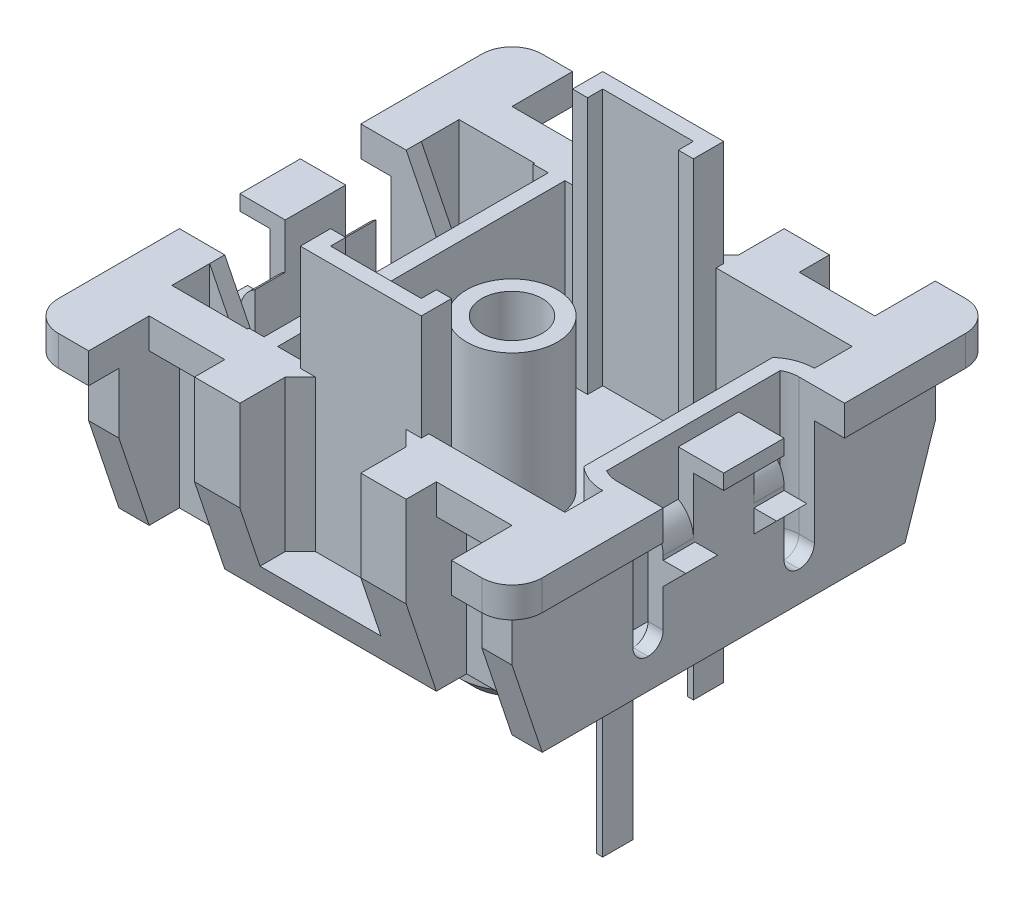
SolidWorks part; units mm, degrees
ref_plane "Plan de face" through (0, 0, 0) normal (0, 0, 1) x (1, 0, 0)
ref_plane "Plan de dessus" through (0, 0, 0) normal (0, 1, 0) x (1, 0, 0)
ref_plane "Plan de droite" through (0, 0, 0) normal (1, 0, 0) x (0, 0, -1)
sketch "Esquisse1" plane through (0, 0, 0) normal (0, 1, 0) x (1, 0, 0)
  line L0 (6, 8) -> (6, 6)
  line L5 (-7, -8) -> (7, -8)
  line L7 (-7, 8) -> (7, 8)
  line L8 (8, -7) -> (8, 7)
  line L9 (-8, -8) -> (8, 8) construction
  line L10 (-8, 8) -> (8, -8) construction
  line L11 (6, 6) -> (3.5, 6)
  line L12 (3.5, 6) -> (3.5, 7)
  line L13 (3.5, 7) -> (2, 7)
  line L14 (2, 7) -> (2, 6.5)
  line L15 (2, 6.5) -> (-2, 6.5)
  line L16 (-2, 6.5) -> (-2, 7)
  line L17 (-2, 7) -> (-3.5, 7)
  line L18 (-3.5, 7) -> (-3.5, 6)
  line L19 (-3.5, 6) -> (-6, 6)
  line L20 (-6, 6) -> (-6, 8)
  line L21 (6, 8) -> (-6, 8)
  line L22 (8, 0) -> (-8, 0)
  line L23 (-8, 0) -> (8, 0)
  line L24 (6, -8) -> (6, -6)
  line L25 (6, -6) -> (3.5, -6)
  line L26 (3.5, -6) -> (3.5, -7)
  line L27 (3.5, -7) -> (2, -7)
  line L28 (2, -7) -> (2, -6.5)
  line L29 (2, -6.5) -> (-2, -6.5)
  line L30 (-2, -6.5) -> (-2, -7)
  line L31 (-2, -7) -> (-3.5, -7)
  line L32 (-3.5, -7) -> (-3.5, -6)
  line L33 (-3.5, -6) -> (-6, -6)
  line L34 (-6, -6) -> (-6, -8)
  line L35 (6, -8) -> (-6, -8)
  line L36 (-8, 3) -> (-7, 3)
  line L37 (-7, 3) -> (-7, 1)
  line L38 (-7, 1) -> (-8, 1)
  line L39 (-8, 1) -> (-8, -1)
  line L40 (-8, -1) -> (-7, -1)
  line L41 (-7, -1) -> (-7, -3)
  line L42 (-7, -3) -> (-8, -3)
  line L43 (-8, -3) -> (-8, 3)
  line L44 (-8, 7) -> (-8, 3)
  line L45 (-8, -7) -> (-8, -3)
  line L46 (0, 6.5) -> (0, -6.5)
  line L47 (0, -6.5) -> (0, 6.5)
  line L48 (-8, -3) -> (-8, -1)
  line L49 (-8, 3) -> (-8, 1)
  line L50 (-8, -7) -> (-8, 7)
  line L51 (8, 3) -> (8, 1)
  line L52 (8, -3) -> (8, -1)
  line L53 (8, -3) -> (8, 3)
  line L54 (7, -3) -> (8, -3)
  line L55 (7, -1) -> (7, -3)
  line L56 (8, -1) -> (7, -1)
  line L57 (8, 1) -> (8, -1)
  line L58 (7, 1) -> (8, 1)
  line L59 (7, 3) -> (7, 1)
  line L60 (8, 3) -> (7, 3)
  line L61 (8, -7) -> (8, 7)
  arc A0 (-8, 7) -> (-7, 8) centre (-7, 7) cw
  arc A1 (8, -7) -> (7, -8) centre (7, -7) cw
  arc A2 (8, 7) -> (7, 8) centre (7, 7) ccw
  arc A3 (-8, -7) -> (-7, -8) centre (-7, -7) ccw
  point P0 (0, 0)
  dimension "D3" = 1
  dimension "D1" = 16
  dimension "D2" = 16
  dimension "D4" = 2
  dimension "D5" = 2
  dimension "D6" = 2.5
  dimension "D7" = 2.5
  dimension "D8" = 4
  dimension "D9" = 1.5
  dimension "D10" = 1.5
  dimension "D11" = 1
  dimension "D12" = 1
  dimension "D13" = 0.5
  dimension "D14" = 0.5
  dimension "D15" = 14
  dimension "D16" = 2
  dimension "D17" = 2
  dimension "D18" = 2
  dimension "D19" = 1
  dimension "D20" = 1
  dimension "D21" = 1
  dimension "D22" = 1
  dimension "D23" = 1
  dimension "D24" = 1
extrude "Boss.-Extru.1" add sketch "Esquisse1" along normal blind 1 contours A0 L44 L36 L37 L38 L39 L23 L46 L15 L16 L17 L18 L19 L20 L7 | L8 A2 L7 L0 L11 L12 L13 L14 L15 L46 L22 L58 L59 L60 | L45 A3 L5 L34 L33 L32 L31 L30 L29 L46 L23 L39 L40 L41 L42 | A1 L8 L54 L55 L56 L22 L46 L29 L28 L27 L26 L25 L24 L5 region at (3.9869, 0, -3.4872) region at (-3.9869, 0, -3.4872) region at (3.9869, 0, 3.4872) region at (-3.9869, 0, 3.4872)
sketch "Esquisse2" plane through (0, 0, 0) normal (0, -1, 0) x (1, 0, 0)
  line L0 (6, 7) -> (6, 5)
  line L1 (-7, 7) -> (7, 7)
  line L2 (-7, 7) -> (-7, -7)
  line L3 (-7, -7) -> (7, -7)
  line L4 (7, 7) -> (7, -7)
  line L5 (-7, 7) -> (7, -7) construction
  line L6 (-7, -7) -> (7, 7) construction
  line L7 (6, 8) -> (6, 6) construction
  line L8 (6, 5) -> (3.5, 5)
  line L9 (3.5, 5) -> (3.5, 7)
  line L10 (3.5, 7) -> (-3.5, 7)
  line L11 (-3.5, 7) -> (-3.5, 5)
  line L12 (-3.5, 5) -> (-6, 5)
  line L13 (-6, 5) -> (-6, 7)
  line L14 (-6, 6) -> (-6, 8) construction
  line L15 (-6, 7) -> (6, 7)
  line L16 (7, 0) -> (-7, 0)
  line L17 (-7, 0) -> (7, 0)
  line L18 (-6, -7) -> (6, -7)
  line L19 (-6, -5) -> (-6, -7)
  line L20 (-3.5, -5) -> (-6, -5)
  line L21 (-3.5, -7) -> (-3.5, -5)
  line L22 (3.5, -7) -> (-3.5, -7)
  line L23 (3.5, -5) -> (3.5, -7)
  line L24 (6, -5) -> (3.5, -5)
  line L25 (6, -7) -> (6, -5)
  point P0 (0, 0)
  line M6 (2, 6.5) -> (-2, 6.5)
  line M7 (-2, 6.5) -> (-2, 7)
  line M8 (-2, 7) -> (-3.5, 7)
  line M9 (-3.5, 7) -> (-3.5, 6)
  line M11 (-6, 6) -> (-6, 8)
  line M16 (-7, 3) -> (-7, 1)
  line M20 (-7, -1) -> (-7, -3)
  line M25 (-6, -8) -> (-6, -6)
  line M27 (-3.5, -6) -> (-3.5, -7)
  line M28 (-3.5, -7) -> (-2, -7)
  line M29 (-2, -7) -> (-2, -6.5)
  line M30 (-2, -6.5) -> (2, -6.5)
  line M31 (2, -6.5) -> (2, -7)
  line M32 (2, -7) -> (3.5, -7)
  line M33 (3.5, -7) -> (3.5, -6)
  line M35 (6, -6) -> (6, -8)
  line M40 (7, -3) -> (7, -1)
  line M44 (7, 1) -> (7, 3)
  line M49 (6, 8) -> (6, 6)
  line M51 (3.5, 6) -> (3.5, 7)
  line M52 (3.5, 7) -> (2, 7)
  line M53 (2, 7) -> (2, 6.5)
  dimension "D1" = 14
  dimension "D2" = 14
  dimension "D3" = 2.5
  dimension "D4" = 2.5
  dimension "D5" = 7
  dimension "D6" = 1
  dimension "D7" = 1
  dimension "D8" = 2
  dimension "D9" = 2
  dimension "D10" = 2
  dimension "D11" = 2
extrude "Boss.-Extru.3" add sketch "Esquisse2" along normal blind 5 contours L16 L4 L1 L0 L8 L9 L11 L12 L13 L2 M44 M49 M51 M52 M53 M6 M7 M8 M9 M11 M16 | L25 L3 L4 L16 L2 L19 L20 L21 L23 L24 M35 M40 M20 M25 M27 M28 M29 M30 M31 M32 M33 region at (0, 0, 3.1337) region at (0, 0, -3.1337)
sketch "Esquisse3" plane through (7, 0, 0) normal (1, 0, 0) x (0, 0, -1)
  line L0 (-7, -2) -> (-6, -5)
  line L1 (-7, -5) -> (-7, 0) construction
  line L2 (-7, -5) -> (7, -5) construction
  line L3 (-6, -5) -> (-7, -5)
  line L4 (-7, -5) -> (-7, -2)
  line L5 (0, 1) -> (0, -5)
  line L6 (-1, 1) -> (1, 1) construction
  line L7 (0, -5) -> (0, 1)
  line L8 (7, -5) -> (7, -2)
  line L9 (6, -5) -> (7, -5)
  line L10 (7, -2) -> (6, -5)
  line M7 (-7, 0) -> (-7, -5)
  line M8 (-7, -5) -> (7, -5)
  line M9 (7, -5) -> (7, 0)
  dimension "D1" = 3
  dimension "D2" = 1
extrude "Enlèv. mat.-Extru.1" cut sketch "Esquisse3" against normal through all contours L0 M7 M8 | L10 M9 M8 region at (7, -4, -6.6667) region at (7, -4, 6.6667)
sketch "Esquisse5" plane through (0, 1, 0) normal (0, 1, 0) x (1, 0, 0)
  line L0 (6.5, 0) -> (-6.5, 0)
  line L1 (6.5, 4.75) -> (-6.5, 4.75)
  line L2 (6.5, 4.75) -> (6.5, -4.75)
  line L3 (6.5, -4.75) -> (-6.5, -4.75)
  line L4 (-6.5, 4.75) -> (-6.5, -4.75)
  line L5 (6.5, 4.75) -> (-6.5, -4.75) construction
  line L6 (6.5, -4.75) -> (-6.5, 4.75) construction
  line L7 (2, 6.5) -> (-2, 6.5)
  line L8 (2, 6.5) -> (2, 4)
  line L10 (-2, 6.5) -> (-2, 4)
  line L12 (1.5, 4) -> (1.5, 4.5)
  line L13 (1.5, 4.5) -> (-1.5, 4.5)
  line L14 (-1.5, 4) -> (-1.5, 4.5)
  line L15 (-4, 4.75) -> (-4, 3.5)
  line L16 (-1.5, -4) -> (-1.5, -4.5)
  line L17 (1.5, -4.5) -> (-1.5, -4.5)
  line L18 (1.5, -4) -> (1.5, -4.5)
  line L20 (-2, -6.5) -> (-2, -4)
  line L22 (2, -6.5) -> (2, -4)
  line L23 (2, -6.5) -> (-2, -6.5)
  line L26 (-3, 4.75) -> (-3, -4.75)
  line L29 (-7, 3) -> (-6.5, 3)
  line L30 (-7, 3) -> (-7, 2)
  line L31 (-7, 2) -> (-6.5, 2)
  line L33 (-7, -3) -> (-6.5, -3)
  line L34 (-7, -3) -> (-7, -2)
  line L35 (-7, -2) -> (-6.5, -2)
  line L37 (7, 3) -> (6.5, 3)
  line L38 (7, 3) -> (7, 2)
  line L39 (7, 2) -> (6.5, 2)
  line L41 (7, -3) -> (6.5, -3)
  line L42 (7, -3) -> (7, -2)
  line L43 (7, -2) -> (6.5, -2)
  line L45 (6.5, 3) -> (6.49, 3)
  line L47 (6.5, -3) -> (6.49, -3)
  line L48 (5.5, 2.01) -> (5.5, -2.01)
  line L49 (-2, 5.25) -> (-1.5, 4.75)
  line L53 (1.5, 4.75) -> (2, 5.5)
  line L54 (-2, -5.25) -> (-1.5, -4.75)
  line L59 (1.5, -4.75) -> (2, -5.5)
  line L60 (-6.5, -3) -> (-4, -3)
  line L61 (-6.5, 3) -> (-4, 3)
  line L63 (-6.5, 3.5) -> (-4, 3.5)
  line L69 (-6.5, -3) -> (-6.5, -3.5)
  line L70 (-6.5, -3.5) -> (-4, -3.5)
  line L72 (-4, 3) -> (-4, -3)
  line L73 (-4, -3.5) -> (-4, -4.75)
  line L74 (-4, -4.75) -> (-4, -3.5)
  line L75 (-2, 4) -> (-1.5, 4)
  line L76 (1.5, 4) -> (2, 4)
  line L77 (-1.5, -4) -> (-2, -4)
  line L78 (1.5, -4) -> (2, -4)
  line L79 (-1.5, -4.75) -> (1.5, -4.75)
  line L80 (-6.5, -3.5) -> (-6.5, -3)
  line L81 (-6.5, 3.5) -> (-6.5, 3)
  line L82 (-4, 4.75) -> (-3, 4.75)
  line L83 (-4, -4.75) -> (-3, -4.75)
  line L84 (7.5, 1.5) -> (6.5, 1.5)
  line L85 (7.5, 3.5) -> (7.5, 1.5)
  line L86 (7.5, 3.5) -> (6.5, 3.5)
  line L87 (6.5, 3.5) -> (6.49, 3.5)
  line L89 (6.5, -3.5) -> (6.49, -3.5)
  line L90 (7.5, -3.5) -> (6.5, -3.5)
  line L91 (7.5, -3.5) -> (7.5, -1.5)
  line L92 (7.5, -1.5) -> (6.5, -1.5)
  line L93 (5.5, 2.01) -> (5.5, 3.1236)
  line L94 (5.5, 3.1236) -> (5.5, -2.01)
  line L95 (5.5, -2.01) -> (5.5, -3.1236)
  line L96 (5.5, -3.1236) -> (5.5, 2.01)
  line L98 (5, 2.01) -> (5, -2.01) construction
  arc A0 (6.49, -3) -> (5.5, -2.01) centre (6.49, -2.01) cw
  arc A1 (6.49, 3) -> (5.5, 2.01) centre (6.49, 2.01) ccw
  arc A2 (6.49, 3.5) -> (5, 2.01) centre (6.49, 2.01) ccw
  arc A3 (6.49, -3.5) -> (5, -2.01) centre (6.49, -2.01) cw
  point P1 (0, 0)
  point P40 (-2, 4.75)
  point P54 (5.5, -3)
  point P57 (5.5, 3)
  dimension "D21" = 0.99
  dimension "D1" = 13
  dimension "D2" = 9.5
  dimension "D3" = 4
  dimension "D4" = 2.5
  dimension "D5" = 0.5
  dimension "D6" = 3
  dimension "D7" = 0.5
  dimension "D8" = 0.5
  dimension "D9" = 1
  dimension "D10" = 1
  dimension "D11" = 0.5
  dimension "D12" = 0.5
  dimension "D13" = 0.5
  dimension "D14" = 1
  dimension "D15" = 1
  dimension "D16" = 1
  dimension "D17" = 0.5
  dimension "D18" = 0.5
  dimension "D19" = 6
  dimension "D20" = 1
  dimension "D22" = 0.5
  dimension "D23" = 0.5
  dimension "D24" = 0.5
  dimension "D27" = 2.5
  dimension "D28" = 0.5
extrude "Enlèv. mat.-Extru.12" cut sketch "Esquisse5" against normal blind 5 contours A1 L45 L2 L1 L8 L76 L12 L13 L14 L75 L10 L26 L0 L48 | L47 A0 L48 L0 L26 L3 L20 L77 L16 L17 L18 L78 L22 L2 | L72 L61 L4 L0 | L72 L0 L4 L60 | L73 L70 L4 L3 | L4 L63 L15 L1 region at (1.4572, 1, 2.3531) region at (1.4572, 1, -2.3531) region at (-5.25, 1, 1.5) region at (-5.25, 1, -1.5) region at (-5.25, 1, -4.125) region at (-5.25, 1, 4.125)
sketch "Esquisse8" plane through (0, 1, -1) normal (0, -1, 0) x (1, 0, 0)
  point P1 (0, 1)
  point P54 (5.5002, -2.0207)
  point P57 (5.488, 3.9793)
  line B0 (6.5, 1) -> (-6.5, 1)
  line B1 (6.5, 6) -> (-6.5, 6)
  line B2 (6.5, 6) -> (6.5, -4)
  line B3 (6.5, -4) -> (-6.5, -4)
  line B4 (-6.5, 6) -> (-6.5, -4)
  line B5 (6.5, 6) -> (-6.5, -4) construction
  line B6 (6.5, -4) -> (-6.5, 6) construction
  line B7 (2, 7.5) -> (-2, 7.5)
  line B8 (2, 7.5) -> (2, 5)
  line B9 (-2, 7.5) -> (-2, 5)
  line B10 (1.5, 5) -> (1.5, 5.5)
  line B11 (1.5, 5.5) -> (-1.5, 5.5)
  line B12 (-1.5, 5) -> (-1.5, 5.5)
  line B13 (-4, 6) -> (-4, 4.5)
  line B14 (-1.5, -3) -> (-1.5, -3.5)
  line B15 (1.5, -3.5) -> (-1.5, -3.5)
  line B16 (1.5, -3) -> (1.5, -3.5)
  line B17 (-2, -5.5) -> (-2, -3)
  line B18 (2, -5.5) -> (2, -3)
  line B19 (2, -5.5) -> (-2, -5.5)
  line B20 (-3, 6) -> (-3, -4)
  line B21 (-7, 4) -> (-6.5, 4)
  line B22 (-7, 4) -> (-7, 3)
  line B23 (-7, 3) -> (-6.5, 3)
  line B24 (-7, -2) -> (-6.5, -2)
  line B25 (-7, -2) -> (-7, -1)
  line B26 (-7, -1) -> (-6.5, -1)
  line B27 (7, 4) -> (6.5, 4)
  line B28 (7, 4) -> (7, 3)
  line B29 (7, 3) -> (6.5, 3)
  line B30 (7, -2) -> (6.5, -2)
  line B31 (7, -2) -> (7, -1)
  line B32 (7, -1) -> (6.5, -1)
  line B33 (6.5, 4) -> (6.49, 4)
  line B34 (6.5, -2) -> (6.49, -2)
  line B35 (5.5, 3.01) -> (5.5, -1.01)
  line B36 (-2, 6.5) -> (-1.5, 6)
  line B37 (1.5, 6) -> (2, 6.5)
  line B38 (-2, -4.5) -> (-1.5, -4)
  line B39 (1.5, -4) -> (2, -4.5)
  line B40 (-6.5, -2) -> (-4, -2)
  line B41 (-6.5, 4) -> (-4, 4)
  line B42 (-6.5, 4.5) -> (-4, 4.5)
  line B43 (-6.5, -2) -> (-6.5, -2.5)
  line B44 (-6.5, -2.5) -> (-4, -2.5)
  line B45 (-4, 4) -> (-4, -2)
  line B46 (-4, -2.5) -> (-4, -4)
  line B47 (-4, -4) -> (-4, -2.5)
  line B48 (-2, 5) -> (-1.5, 5)
  line B49 (1.5, 5) -> (2, 5)
  line B50 (-1.5, -3) -> (-2, -3)
  line B51 (1.5, -3) -> (2, -3)
  line B52 (-1.5, -4) -> (1.5, -4)
  line B53 (-6.5, -2.5) -> (-6.5, -2)
  line B54 (-6.5, 4.5) -> (-6.5, 4)
  line B55 (-4, 6) -> (-3, 6)
  line B56 (-4, -4) -> (-3, -4)
  arc B57 (6.49, -2) -> (5.5, -1.01) centre (6.49, -1.01) cw
  arc B58 (6.49, 4) -> (5.5, 3.01) centre (6.49, 3.01) ccw
  dimension "D19" = 6
  dimension "D20" = 1
sketch_block_instance "Bloc1-1"
sketch_block "Bloc1" parameters "D18"=0.99, "D1"=13, "D2"=10, "D3"=4, "D4"=2.5, "D5"=0.5, "D6"=3, "D7"=0.5, "D8"=0.5, "D9"=1, "D10"=1, "D11"=0.5, "D12"=0.5, "D13"=1, "D14"=1, "D15"=1, "D16"=0.5, "D17"=0.5, "D19"=0.5, "D20"=0.5, "D21"=2.5, "D22"=0.5, "D23"=0.5
extrude "Enlèv. mat.-Extru.17" cut sketch "Esquisse8" along normal blind 5 contours B3 B39 B18 B19 B17 B38 | B37 B1 B36 B9 B7 B8 region at (0, 1, 5.7754) region at (0, 1, -5.7754)
sketch "Esquisse10" plane through (0, 1, 0) normal (0, 1, 0) x (1, 0, 0)
  line L5 (0, 4.5) -> (0, -4.5)
  line L10 (1.5, 4.5) -> (-1.5, 4.5) construction
  line L11 (1.5, -4.5) -> (-1.5, -4.5) construction
  line L12 (0, -4.5) -> (0, 4.5)
  line L22 (-8, 3) -> (-5, 3)
  line L23 (-8, 3) -> (-8, 2)
  line L24 (-8, 2) -> (-5, 2)
  line L25 (-5, 3) -> (-5, 2)
  line L26 (-8, -3) -> (-5, -3)
  line L27 (-8, -3) -> (-8, -2)
  line L28 (-8, -2) -> (-5, -2)
  line L29 (-5, -3) -> (-5, -2)
  dimension "D1" = 3
  dimension "D2" = 1
  dimension "D3" = 3
  dimension "D4" = 1
extrude "Enlèv. mat.-Extru.20" cut sketch "Esquisse10" against normal blind 5 contours L25 L22 L23 L24 | L26 L29 L28 L27 region at (-6.5, 1, -2.5) region at (-6.5, 1, 2.5)
sketch "Esquisse11" plane through (0, 1, 0) normal (0, 1, 0) x (1, 0, 0)
sketch "Esquisse12" plane through (0, 1, 0) normal (0, 1, 0) x (1, 0, 0)
  line L1 (6.49, -3) -> (7, -3)
  line L2 (6, 2.8702) -> (6, -2.8702)
  line L3 (6, 2.8702) -> (6, -2.8702)
  line L4 (7, -3) -> (7, -2)
  line L5 (7, -1) -> (7, -3) construction
  line L6 (7, -2) -> (6.5, -2)
  line L7 (6.5, -2) -> (6.5, 2)
  line L8 (6.5, 2) -> (7, 2)
  line L9 (7, 3) -> (7, 1) construction
  line L10 (7, 2) -> (7, 3)
  line L11 (7, 3) -> (6.49, 3)
  arc A8 (6, -2.8702) -> (6.49, -3) centre (6.49, -2.01) ccw
  arc A9 (6.49, 3) -> (6, 2.8702) centre (6.49, 2.01) ccw
  arc A10 (6, -2.8702) -> (6.49, -3) centre (6.49, -2.01) ccw
  arc A11 (6.49, 3) -> (6, 2.8702) centre (6.49, 2.01) ccw
  dimension "D2" = 4
  dimension "D3" = 1
  dimension "D4" = 1
  dimension "D5" = 0.5
  dimension "D6" = 0.5
  dimension "D1" = 0.5
extrude "Enlèv. mat.-Extru.21" cut sketch "Esquisse12" against normal blind 5
sketch "Esquisse13" plane through (0, -5, 0) normal (0, -1, 0) x (1, 0, 0)
  circle A0 centre (0, 0) radius 1.75
  dimension "D1" = 3.5
extrude "Boss.-Extru.4" add sketch "Esquisse13" along normal blind 4
chamfer "Chanfrein1" distance 0.5 1 edges at (0, -9, -1.75)
sketch "Esquisse14" plane through (0, -9, 0) normal (0, -1, 0) x (1, 0, 0)
  circle A0 centre (0, 0) radius 0.75
  dimension "D1" = 1.5
extrude "Enlèv. mat.-Extru.22" cut sketch "Esquisse14" against normal blind 0.1
sketch "Esquisse15" plane through (0, -4, 0) normal (0, 1, 0) x (1, 0, 0)
  circle A0 centre (0, 0) radius 1
  circle A1 centre (0, 0) radius 1.5
  dimension "D1" = 2
  dimension "D2" = 3
extrude "Boss.-Extru.5" add sketch "Esquisse15" along normal blind 5
sketch "Esquisse16" plane through (0, -4, 0) normal (0, 1, 0) x (1, 0, 0)
  circle A0 centre (0, 0) radius 1
extrude "Enlèv. mat.-Extru.23" cut sketch "Esquisse16" against normal blind 4
sketch "Esquisse17" plane through (0, -5, 0) normal (0, -1, 0) x (1, 0, 0)
  line L1 (3, -4) -> (2.8, -4)
  line L2 (3, -4) -> (3, -3)
  line L3 (3, -3) -> (2.8, -3)
  line L4 (2.8, -4) -> (2.8, -3)
  line L5 (6, 3) -> (5.8, 3)
  line L6 (6, 3) -> (6, 2)
  line L7 (6, 2) -> (5.8, 2)
  line L8 (5.8, 3) -> (5.8, 2)
  dimension "D1" = 1
  dimension "D2" = 0.2
  dimension "D3" = 1
  dimension "D4" = 0.2
extrude "Boss.-Extru.6" add sketch "Esquisse17" along normal blind 5 contours L6 L7 L8 L5 | L2 L3 L4 L1
sketch "Esquisse18" plane through (0, 0, 3.5) normal (0, 0, 1) x (1, 0, 0)
  line L0 (-6.5, 1) -> (-6.5, -1)
  line L1 (-6.5, -4) -> (-6.5, 1) construction
  line L2 (-6.5, -1) -> (-5.5, -1)
  line L3 (-5.5, -1) -> (-4.5, -1)
  line L4 (-4.5, -1) -> (-3.5, -1)
  line L5 (-3.5, -1) -> (-3.5, 1)
  line L6 (-3.5, 1) -> (-4.5, -1)
  line L7 (-5.5, -1) -> (-6.5, 1)
  line L8 (-3.5, 1) -> (-6.5, 1)
  line M6 (-4, 1) -> (-6.5, 1)
  line M9 (-4, -4) -> (-4, 1)
  dimension "D1" = 3
  dimension "D2" = 1
  dimension "D3" = 1
  dimension "D4" = 1
  dimension "D5" = 2
extrude "Enlèv. mat.-Extru.24" cut sketch "Esquisse18" against normal blind 8.2 and the other way blind 1.2 contours L7 L3 L6 M9 M6 | L6 L8 M9 region at (-5.0778, 0.1333, 3.5) region at (-3.8333, 0.6667, 3.5)
sketch "Esquisse19" plane through (0, 1, 0) normal (0, 1, 0) x (1, 0, 0)
  line L1 (2, 4) -> (-2, 4)
  line L2 (2, 4) -> (2, 5)
  line L3 (2, 5) -> (-2, 5)
  line L4 (-2, 4) -> (-2, 5)
  line L5 (2, -4) -> (-2, -4)
  line L6 (2, -4) -> (2, -5)
  line L7 (2, -5) -> (-2, -5)
  line L8 (-2, -4) -> (-2, -5)
  line L9 (-1.5, 4.5) -> (1.5, 4.5)
  line L10 (-1.5, 4.5) -> (-1.5, 4)
  line L11 (-1.5, 4) -> (1.5, 4)
  line L12 (1.5, 4.5) -> (1.5, 4)
  line L13 (1.5, -4) -> (-1.5, -4)
  line L14 (1.5, -4) -> (1.5, -4.5)
  line L15 (1.5, -4.5) -> (-1.5, -4.5)
  line L16 (-1.5, -4) -> (-1.5, -4.5)
  dimension "D1" = 4
  dimension "D2" = 1
  dimension "D3" = 1
  dimension "D4" = 4
extrude "Boss.-Extru.7" add sketch "Esquisse19" along normal blind 3.5 contours L9 L12 L1 L2 L3 L4 L10 | L16 L5 L8 L7 L6 L14 L15 region at (0, 1, -4.65) region at (0, 1, 4.65)
sketch "Esquisse20" plane through (0, 1, 0) normal (0, 1, 0) x (1, 0, 0)
  line L0 (-6.5, 2) -> (-6.5, -2) construction
  line L1 (-7, 2) -> (-6.5, 2)
  line L2 (-7, 2) -> (-7, 1)
  line L3 (-7, 1) -> (-6.5, 1)
  line L4 (-6.5, 2) -> (-6.5, 1)
  line L5 (6.5, -2) -> (6.5, 2) construction
  line L6 (-7, -1) -> (-6.5, -1)
  line L7 (-7, -1) -> (-7, -2)
  line L8 (-7, -2) -> (-6.5, -2)
  line L9 (-6.5, -1) -> (-6.5, -2)
  line L10 (7, 1) -> (6.5, 1)
  line L11 (7, 1) -> (7, 2)
  line L12 (7, 2) -> (6.5, 2)
  line L13 (6.5, 1) -> (6.5, 2)
  line L14 (7, -2) -> (6.5, -2)
  line L15 (7, -2) -> (7, -1)
  line L16 (7, -1) -> (6.5, -1)
  line L17 (6.5, -2) -> (6.5, -1)
extrude "Enlèv. mat.-Extru.25" cut sketch "Esquisse20" against normal blind 1.5
sketch "Esquisse22" plane through (-7, 0, 0) normal (-1, 0, 0) x (0, 0, 1)
  line L0 (-2, -0.5) -> (-2, -4) construction
  line L1 (-2, -1.5) -> (-1, -1.5)
  line L2 (-2, -1.5) -> (-2, -2.25)
  line L3 (-2, -2.25) -> (-1, -2.25)
  line L4 (-1, -1.5) -> (-1, -2.25)
  line L5 (2, -0.5) -> (2, -4) construction
  line L6 (2, -1.5) -> (1, -1.5)
  line L7 (2, -1.5) -> (2, -2.25)
  line L8 (2, -2.25) -> (1, -2.25)
  line L9 (1, -1.5) -> (1, -2.25)
  dimension "D1" = 0.75
  dimension "D2" = 0.75
  dimension "D3" = 1
  dimension "D4" = 1
extrude "Boss.-Extru.8" add sketch "Esquisse22" along normal blind 0.75
chamfer "Chanfrein2" distance 0.75 angle 45 2 edges at (-7.75, -2.25, 1.5) (-7.75, -2.25, -1.5)
fillet "Congé1" radius 1 2 edges at (-7, -0.5, -1.5) (-7, -0.5, 1.5) first distance on face at (-7, -1.8077, 0)
sketch "Esquisse23" plane through (0, 0, 0) normal (0, -1, 0) x (1, 0, 0)
  line L0 (-7, 6) -> (-7, -6) construction
  line L1 (-8, 1) -> (-7, 1)
  line L2 (-8, 1) -> (-8, -1)
  line L3 (-8, -1) -> (-7, -1)
  line L4 (-7, 1) -> (-7, -1)
  line L5 (-7, 1) -> (-7, -1) construction
extrude "Enlèv. mat.-Extru.26" cut sketch "Esquisse23" against normal blind 0.5
sketch "Esquisse24" plane through (7, 0, 0) normal (1, 0, 0) x (0, 0, -1)
  line L0 (-2, -4) -> (-2, -0.5) construction
  line L1 (2, -4) -> (2, -0.5) construction
  line L2 (-2, -1.5) -> (-0.9498, -1.5)
  line L3 (-2, -1.5) -> (-2, -2.25)
  line L4 (-2, -2.25) -> (-0.9498, -2.25)
  line L5 (-0.9498, -1.5) -> (-0.9498, -2.25)
  line L6 (2, -1.5) -> (1, -1.5)
  line L7 (2, -1.5) -> (2, -2.25)
  line L8 (2, -2.25) -> (1, -2.25)
  line L9 (1, -1.5) -> (1, -2.25)
  dimension "D1" = 0.75
  dimension "D2" = 0.75
  dimension "D3" = 1
  dimension "D4" = 1.0502
extrude "Boss.-Extru.9" add sketch "Esquisse24" along normal blind 0.75
chamfer "Chanfrein3" distance 0.75 angle 45 2 edges at (7.75, -2.25, 1.4749) (7.75, -2.25, -1.5)
fillet "Congé2" radius 1 2 edges at (7, -0.5, -1.5) (7, -0.5, 1.5) first distance on face at (7, -1.8077, -0.0039)
sketch "Esquisse25" plane through (0, 0, 0) normal (0, -1, 0) x (1, 0, 0)
  line L1 (8, 1) -> (7, 1)
  line L2 (8, 1) -> (8, -1)
  line L3 (8, -1) -> (7, -1)
  line L4 (7, 1) -> (7, -1)
extrude "Enlèv. mat.-Extru.27" cut sketch "Esquisse25" against normal blind 0.5
fillet "Congé3" radius 0.5 10 edges at (6.2366, -4, 2.967) (6.2366, -4, -2.967) (-6.75, -4, -2) (-5.5, -4, -3) (-5.5, -4, 3) (-6.75, -4, 2) (6.75, -4, 2) (6.745, -4, 3) (6.745, -4, -3) (6.75, -4, -2)
